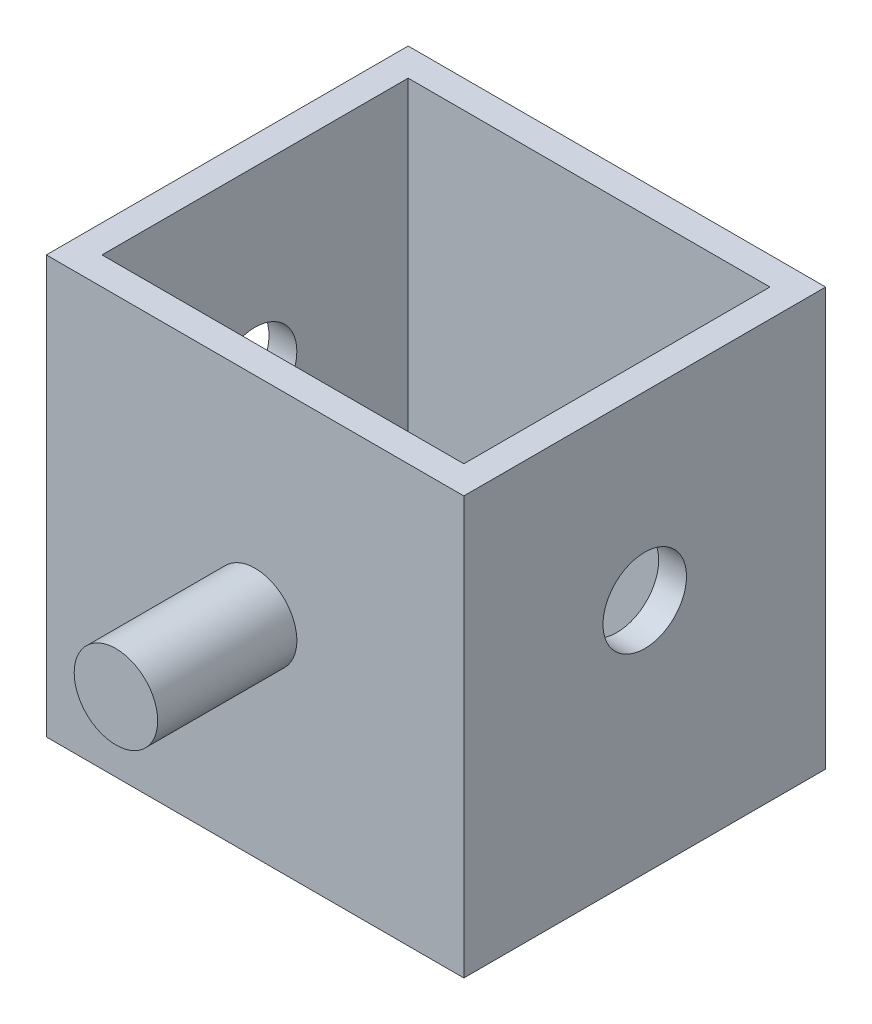
SolidWorks part; units mm, degrees
ref_plane "Front Plane" through (0, 0, 0) normal (0, 0, 1) x (1, 0, 0)
ref_plane "Top Plane" through (0, 0, 0) normal (0, 1, 0) x (1, 0, 0)
ref_plane "Right Plane" through (0, 0, 0) normal (1, 0, 0) x (0, 0, -1)
sketch "Sketch1" plane through (0, 0, 0) normal (0, 0, 1) x (1, 0, 0)
  line L1 (-19.05, -19.05) -> (19.05, -19.05)
  line L2 (-19.05, -19.05) -> (-19.05, 19.05)
  line L3 (-19.05, 19.05) -> (19.05, 19.05)
  line L4 (19.05, -19.05) -> (19.05, 19.05)
  line L5 (-19.05, -19.05) -> (19.05, 19.05) construction
  line L6 (-19.05, 19.05) -> (19.05, -19.05) construction
  point P0 (0, 0)
  dimension "D1" = 38.1
  dimension "D2" = 38.1
extrude "main body" add sketch "Sketch1" along normal blind 33.02
shell "hollow it" thickness 2.54 removed face at (0, 19.05, 16.51)
ref_point "cut point"
sketch "Sketch2" plane through (19.05, 0, 0) normal (1, 0, 0) x (0, 0, -1)
  line L1 (-33.02, -19.05) -> (0, -19.05) construction
  circle A0 centre (-16.51, 2.54) radius 3.81
  dimension "D1" = 21.59
ref_point "bigger nibble point"
ref_point "bigger nibble here, too"
sketch "Sketch3" plane through (0, 0, 33.02) normal (0, 0, 1) x (1, 0, 0)
  circle A0 centre (0, 0) radius 3.81
  dimension "D1" = 7.62
extrude "nibble no 1" add sketch "Sketch3" along normal blind 12.7
sketch "Sketch4" plane through (0, 0, 0) normal (0, 0, -1) x (-1, 0, 0)
  circle A0 centre (0, 0) radius 3.81
  dimension "D1" = 7.62
extrude "nibble no 2" add sketch "Sketch4" along normal blind 12.7
ref_point "nibble center"
ref_plane "nibble flag plane" through (0, 0, 0) normal (0, -1, 0) x (-1, 0, 0)
sketch "Sketch5" plane through (0, 0, 0) normal (0, -1, 0) x (-1, 0, 0)
  line L1 (-0.8217, 4.4483) -> (0.4483, 4.4483)
  line L2 (-0.8217, 4.4483) -> (-0.8217, 8.2583)
  line L3 (-0.8217, 8.2583) -> (0.4483, 8.2583)
  line L4 (0.4483, 4.4483) -> (0.4483, 8.2583)
  line L5 (-0.8217, 4.4483) -> (0.4483, 8.2583) construction
  line L6 (-0.8217, 8.2583) -> (0.4483, 4.4483) construction
  point P0 (-0.1867, 6.3533)
  dimension "D1" = 1.27
  dimension "D2" = 3.81
extrude "flag" add sketch "Sketch5" along normal blind 0.254
extrude "nibble holes" cut sketch "Sketch2" against normal through all
